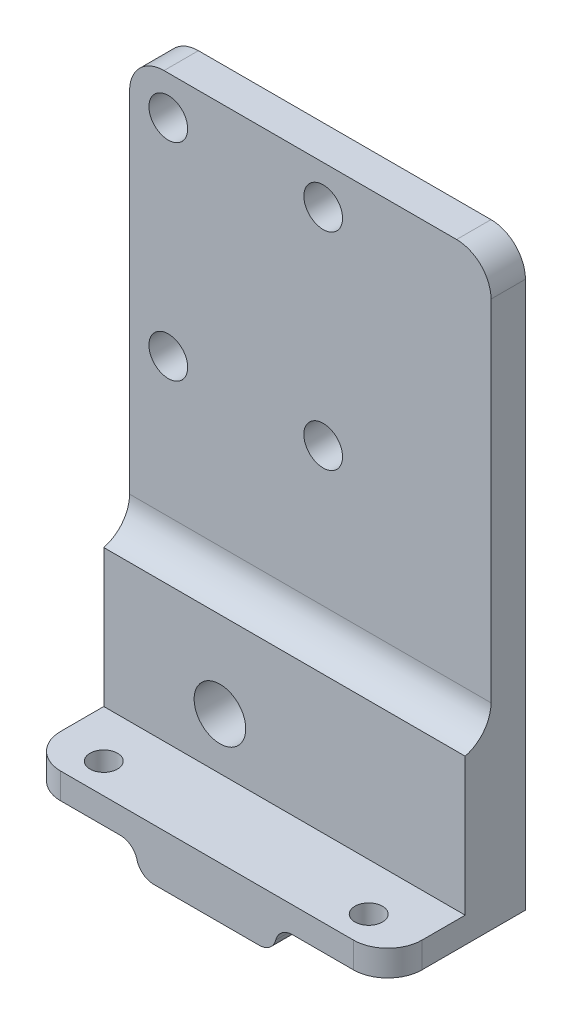
SolidWorks part; units mm, degrees
ref_plane "Front Plane" through (0, 0, 0) normal (0, 0, 1) x (1, 0, 0)
ref_plane "Top Plane" through (0, 0, 0) normal (0, 1, 0) x (1, 0, 0)
ref_plane "Right Plane" through (0, 0, 0) normal (1, 0, 0) x (0, 0, -1)
sketch "Sketch1" plane through (0, 0, 0) normal (0, 0, 1) x (1, 0, 0)
  line L0 (-27.8148, -30.75) -> (34.6603, -30.75) construction
  line L1 (-21, 33.75) -> (21, 33.75)
  line L2 (-21, 33.75) -> (-21, -33.75)
  line L3 (-21, -33.75) -> (21, -33.75)
  line L4 (21, 33.75) -> (21, -33.75)
  line L5 (-21, 33.75) -> (21, -33.75) construction
  line L6 (-21, -33.75) -> (21, 33.75) construction
  line L7 (-32.8561, -24.75) -> (47.5289, -24.75) construction
  line L8 (-15.5, 42.3879) -> (-15.5, -56.6392) construction
  line L9 (15.5, 39.8381) -> (15.5, -54.264) construction
  line L10 (0, 36.2841) -> (0, -52.3905) construction
  line L11 (-7.5, 36.2841) -> (-7.5, -44.8265) construction
  line L12 (-36.2529, -10.25) -> (40.3361, -10.25) construction
  line L13 (-44.7598, 29.25) -> (42.6416, 29.25) construction
  line L14 (-48.0587, 5.25) -> (52.0206, 5.25) construction
  line L15 (-16.5, 42.3879) -> (-16.5, -39.2321) construction
  line L16 (1.5, 42.3879) -> (1.5, -39.2321) construction
  circle A0 centre (-7.5, -24.75) radius 3
  circle A1 centre (1.5, 29.25) radius 2.25
  circle A2 centre (-16.5, 29.25) radius 2.25
  circle A3 centre (1.5, 5.25) radius 2.25
  circle A4 centre (-16.5, 5.25) radius 2.25
  point P0 (0, 0)
  dimension "D7" = 6
  dimension "D14" = 4.5
  dimension "D1" = 42
  dimension "D2" = 3
  dimension "D3" = 6
  dimension "D4" = 31
  dimension "D5" = 15.5
  dimension "D6" = 8
  dimension "D8" = 14.5
  dimension "D9" = 44
  dimension "D10" = 4.5
  dimension "D11" = 24
  dimension "D12" = 9
  dimension "D13" = 9
extrude "Boss-Extrude1" add sketch "Sketch1" along normal blind 4
sketch "Sketch2" plane through (0, 0, 4) normal (0, 0, 1) x (1, 0, 0)
  line L0 (-21, -30.75) -> (21, -30.75)
  line L1 (-21, 33.75) -> (-21, -33.75) construction
  line L2 (21, -33.75) -> (21, 33.75) construction
  line L3 (-21, -33.75) -> (21, -33.75) construction
  line L4 (-21, -30.75) -> (-21, -33.75)
  line L5 (21, -33.75) -> (21, -30.75)
  line L6 (-21, -33.75) -> (21, -33.75)
  dimension "D1" = 3
extrude "Boss-Extrude2" add sketch "Sketch2" along normal blind 12
sketch "Sketch3" plane through (0, 0, 4) normal (0, 0, 1) x (1, 0, 0)
  line L0 (-21, -30.75) -> (-21, -14.75)
  line L1 (-21, 33.75) -> (-21, -30.75) construction
  line L2 (-21, -14.75) -> (21, -14.75)
  line L3 (21, -30.75) -> (21, 33.75) construction
  line L4 (21, -14.75) -> (21, -30.75)
  line L5 (21, -30.75) -> (-21, -30.75)
  circle A0 centre (-7.5, -24.75) radius 3 construction
  circle A1 centre (-7.5, -24.75) radius 3
  dimension "D1" = 16
extrude "Boss-Extrude3" add sketch "Sketch3" along normal blind 3
sketch "Sketch4" plane through (0, -33.75, 0) normal (0, -1, 0) x (1, 0, 0)
  line L0 (0, 20.1545) -> (0, -6.5787) construction
  line L1 (-15.5, 20.1545) -> (-15.5, -7.1847) construction
  line L2 (15.2857, 20.8952) -> (15.2857, -7.1847) construction
  line L3 (-26.8005, 12.5) -> (25.9925, 12.5) construction
  line L4 (-21, 16) -> (21, 16) construction
  circle A0 centre (-15.5, 12.5) radius 1.6
  circle A1 centre (15.2857, 12.5) radius 1.6
  dimension "D4" = 3.2
  dimension "D1" = 15.2857
  dimension "D2" = 15.5
  dimension "D3" = 3.5
extrude "Cut-Extrude1" cut sketch "Sketch4" against normal up to next
fillet "Fillet1" radius 4 5 edges at (21, -32.25, 16) (-21, -32.25, 16) (21, 33.75, 2) (-21, 33.75, 2) (0, -14.75, 4)
sketch "Sketch5" plane through (0, -33.75, 0) normal (0, -1, 0) x (1, 0, 0)
  line L0 (-21, 0) -> (21, 0) construction
  line L1 (-8.0718, 0) -> (7.9282, 0)
  line L2 (-8.0718, 0) -> (-8.0718, 16)
  line L3 (-8.0718, 16) -> (7.9282, 16)
  line L4 (7.9282, 0) -> (7.9282, 16)
  line L5 (-17, 16) -> (17, 16) construction
  point P8 (-0.0718, 0)
  dimension "D1" = 8
extrude "Boss-Extrude4" add sketch "Sketch5" along normal blind 3
fillet "Fillet3" radius 2 2 edges at (7.9282, -33.75, 8) (-8.0718, -33.75, 8)
fillet "Fillet4" radius 2 2 edges at (7.9282, -36.75, 8) (-8.0718, -36.75, 8)
